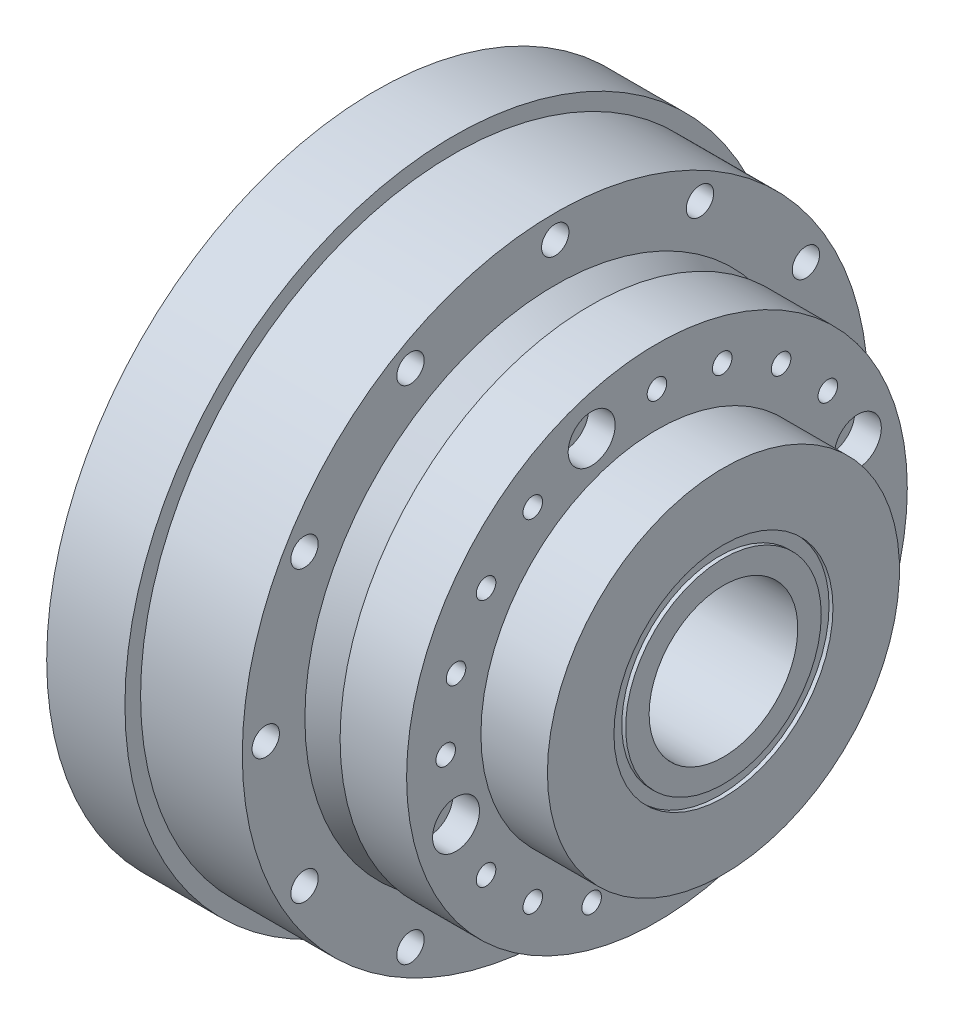
SolidWorks part; units mm, degrees
ref_plane "前视基准面" through (0, 0, 0) normal (0, 0, 1) x (1, 0, 0)
ref_plane "上视基准面" through (0, 0, 0) normal (0, 1, 0) x (1, 0, 0)
ref_plane "右视基准面" through (0, 0, 0) normal (1, 0, 0) x (0, 0, -1)
sketch "草图1" plane through (0, 0, 0) normal (0, 0, 1) x (1, 0, 0)
  line L0 (-65.2008, 0) -> (80.5899, 0) construction
  line L1 (0, 9.5) -> (0, 12.5)
  line L2 (0, 12.5) -> (12, 12.5)
  line L3 (12, 12.5) -> (12, 42)
  line L4 (12, 42) -> (22, 42)
  line L5 (22, 42) -> (22, 40)
  line L6 (22, 40) -> (35, 40)
  line L7 (35, 40) -> (35, 32)
  line L9 (39.5, 29.4019) -> (39.5, 32)
  line L10 (39.5, 32) -> (48, 32)
  line L11 (48, 32) -> (48, 22.5)
  line L12 (48, 22.5) -> (56.5, 22.5)
  line L13 (56.5, 22.5) -> (56.5, 9.5)
  line L14 (0, 9.5) -> (56.5, 9.5)
  line L15 (0, 0) -> (0, 43.251) construction
  line L17 (35, 32) -> (39.5, 29.4019)
  dimension "D1" = 84
  dimension "D2" = 25
  dimension "D3" = 19
  dimension "D4" = 80
  dimension "D5" = 64
  dimension "D6" = 45
  dimension "D7" = 12
  dimension "D8" = 10
  dimension "D9" = 23
  dimension "D10" = 56.5
  dimension "D11" = 8.5
  dimension "D12" = 8.5
  dimension "D13" = 60
revolve "旋转1" add sketch "草图1" angle 360 about L0
ref_axis "基准轴1" through (56.5, 0, 0) along (-1, 0, 0)
sketch "草图5" plane through (12, 0, 0) normal (-1, 0, 0) x (0, 0, 1)
  line L0 (0, 0) -> (0, 40.0957) construction
  circle A0 centre (0, 0) radius 37 construction
  circle A1 centre (0, 37) radius 1.75
  dimension "D1" = 74
  dimension "D2" = 3.5
extrude "切除-拉伸1" cut sketch "草图5" against normal up to next
pattern_circular "阵列(圆周)2" count 12 over 360 about axis through (56.5, 0, 0) along (-1, 0, 0) of "切除-拉伸1"
sketch "草图9" plane through (12, 0, 0) normal (-1, 0, 0) x (0, 0, 1)
  circle A0 centre (0, 0) radius 22.5
  circle A1 centre (0, 0) radius 10
  dimension "D1" = 45
extrude "凸台-拉伸1" add sketch "草图9" along normal blind 5.5 contours A1 | A0
ref_plane "基准面1" through (0, 12.5, 0) normal (0, 1, 0) x (1, 0, 0)
hole_wizard "M3 螺纹孔3" positions "草图11" profile "草图10" tap size "M3" standard "GB"
sketch "草图11" plane through (0, 12.5, 0) normal (0, 1, 0) x (1, 0, 0)
  line L0 (56.5, 0) -> (0, 0) construction
  line L1 (0, 12.5) -> (0, -12.5) construction
  point P0 (2.5, 0)
  dimension "D1" = 2.5
sketch "草图10" plane through (2.5, 12.5, 0) normal (1, 0, 0) x (0, 0, 1)
  line L0 (0, 0) -> (0, 7.2511)
  line L1 (0, 7.2511) -> (1.25, 6.5)
  line L2 (1.25, 6.5) -> (1.25, 0)
  line L5 (1.25, 0) -> (0, 0)
  line L10 (0, 7.2511) -> (-1.25, 6.5) construction
  line L11 (0, -6.35) -> (0, 107.95) construction
  dimension "螺纹孔钻头直径" = 2.5
  dimension "螺纹孔钻头深度" = 6.5
  dimension "导头角度" = 118
cosmetic thread "孔螺蚊线4" parameters "D1"=3.1125, "D2"=3
pattern_circular "阵列(圆周)4" count 3 over 360 about axis through (56.5, 0, 0) along (-1, 0, 0) of "M3 螺纹孔3"
sketch "草图12" plane through (56.5, 0, 0) normal (1, 0, 0) x (0, 0, -1)
  circle A0 centre (0, 0) radius 14
  circle A1 centre (0, 0) radius 12.5
  dimension "D1" = 25
  dimension "D2" = 28
extrude "切除-拉伸4" cut sketch "草图12" against normal blind 0.5 contours A0 | A1
sketch "草图14" plane through (6.5, 0, 0) normal (-1, 0, 0) x (0, 0, 1)
  circle A0 centre (0, 0) radius 12.5
  circle A1 centre (0, 0) radius 14
  dimension "D1" = 25
  dimension "D2" = 28
extrude "切除-拉伸5" cut sketch "草图14" against normal blind 0.5
hole_wizard "M3 螺纹孔4" positions "草图16" profile "草图15" tap size "M3" standard "GB"
sketch "草图16" plane through (48, 0, 0) normal (1, 0, 0) x (0, 0, -1)
  line L0 (0, 0) -> (0, 44.049) construction
  circle A0 centre (0, 0) radius 27 construction
  point P0 (0, 27)
  dimension "D1" = 54
sketch "草图15" plane through (48, 27, 0) normal (0, 1, 0) x (0, 0, -1)
  line L0 (0, 0) -> (0, 12.7511)
  line L1 (0, 12.7511) -> (1.25, 12)
  line L2 (1.25, 12) -> (1.25, 0)
  line L5 (1.25, 0) -> (0, 0)
  line L10 (0, 12.7511) -> (-1.25, 12) construction
  line L11 (0, -6.35) -> (0, 107.95) construction
  dimension "螺纹孔钻头直径" = 2.5
  dimension "螺纹孔钻头深度" = 12
  dimension "导头角度" = 118
cosmetic thread "孔螺蚊线5" parameters "D1"=6, "D2"=3
pattern_circular "阵列(圆周)5" count 4 every 18 about axis through (56.5, 0, 0) along (-1, 0, 0) of "M3 螺纹孔4"
pattern_circular "阵列(圆周)6" count 4 over 360 about axis through (56.5, 0, 0) along (-1, 0, 0) of "阵列(圆周)5"
hole_wizard "打孔尺寸(%根据)内六角圆柱头螺钉的类型1" positions "草图18" profile "草图17" counterbore size "M3" standard "GB"
sketch "草图18" plane through (48, 0, 0) normal (1, 0, 0) x (0, 0, -1)
  line L0 (0, 0) -> (0, 44.2452) construction
  line L2 (0, 0) -> (-14.269, 43.9156) construction
  circle A0 centre (0, 0) radius 27 construction
  point P0 (-8.3435, 25.6785)
  dimension "D1" = 18
sketch "草图17" plane through (48, 25.6785, 8.3435) normal (0, 1, 0) x (0, 0, -1)
  line L0 (0, 0) -> (0, 16.5215)
  line L1 (0, 16.5215) -> (1.7, 15.5)
  line L2 (1.7, 15.5) -> (1.7, 3.4)
  line L3 (1.7, 3.4) -> (3, 3.4)
  line L4 (3, 3.4) -> (3, 0)
  line L5 (3, 0) -> (0, 0)
  line L10 (0, 16.5215) -> (-1.7, 15.5) construction
  line L11 (0, -6.35) -> (0, 107.95) construction
  dimension "孔直径" = 3.4
  dimension "孔深度" = 15.5
  dimension "柱形沉头孔直径" = 6
  dimension "柱形沉头孔深度" = 3.4
  dimension "导头角度" = 118
pattern_circular "阵列(圆周)7" count 4 over 360 about axis through (56.5, 0, 0) along (-1, 0, 0) of "打孔尺寸(%根据)内六角圆柱头螺钉的类型1"
